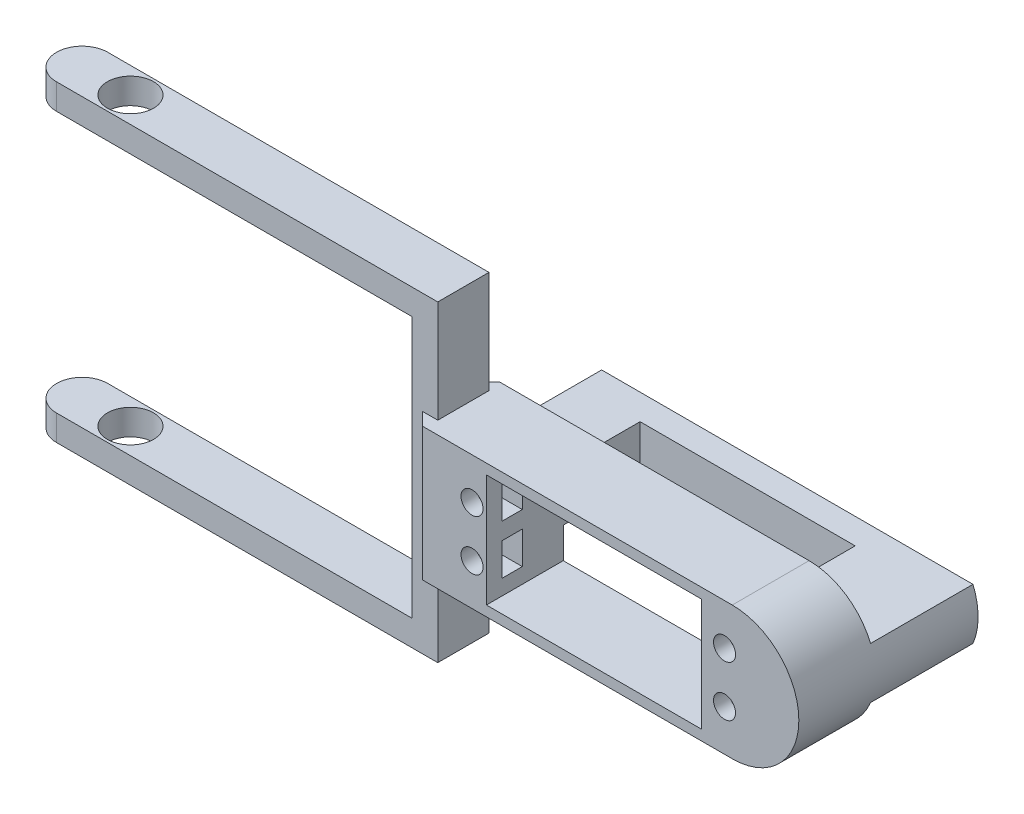
SolidWorks part; units mm, degrees
ref_plane "Plan de face" through (0, 0, 0) normal (0, 0, 1) x (1, 0, 0)
ref_plane "Plan de dessus" through (0, 0, 0) normal (0, 1, 0) x (1, 0, 0)
ref_plane "Plan de droite" through (0, 0, 0) normal (1, 0, 0) x (0, 0, -1)
sketch "Esquisse1" plane through (0, 0, 0) normal (0, 0, 1) x (1, 0, 0)
  line L1 (30, -13) -> (-30, -13)
  line L3 (30, 13) -> (-30, 13)
  line L4 (-30, -13) -> (-30, 13)
  line L5 (30, -13) -> (-30, 13) construction
  line L6 (30, 13) -> (-30, -13) construction
  arc A0 (30, -13) -> (30, 13) centre (30, 0) ccw
  point P0 (0, 0)
  dimension "D1" = 60
  dimension "D2" = 26
extrude "Boss.-Extru.1" add sketch "Esquisse1" along normal blind 15
sketch "Esquisse2" plane through (0, 0, 15) normal (0, 0, 1) x (1, 0, 0)
  line L0 (-30, 13) -> (-30, -13) construction
  line L1 (-18, 11) -> (24, 11)
  line L2 (-18, 11) -> (-18, -11)
  line L3 (-18, -11) -> (24, -11)
  line L4 (24, 11) -> (24, -11)
  point P4 (-18, 0)
  dimension "D1" = 42
  dimension "D2" = 22
  dimension "D3" = 12
extrude "Enlèv. mat.-Extru.1" cut sketch "Esquisse2" against normal through all
sketch "Esquisse4" plane through (0, 0, 15) normal (0, 0, 1) x (1, 0, 0)
  circle A0 centre (-20.81, 4.935) radius 2.15
  circle A1 centre (-20.81, -4.935) radius 2.15
  circle A2 centre (28.49, 4.935) radius 2.15
  circle A3 centre (28.49, -4.935) radius 2.15
extrude "Enlèv. mat.-Extru.2" cut sketch "Esquisse4" against normal blind 3
sketch "Esquisse5" plane through (-18, 0, 0) normal (1, 0, 0) x (0, 0, -1)
  line L1 (-12, -8) -> (-8, -8)
  line L2 (-12, -8) -> (-12, -1.65)
  line L3 (-12, -1.65) -> (-8, -1.65)
  line L4 (-8, -8) -> (-8, -1.65)
  line L5 (-15, 11) -> (-15, -11) construction
  line L6 (0, -11) -> (-15, -11) construction
  line L7 (-16.3207, 0) -> (1.751, 0) construction
  line L8 (-12, 1.65) -> (-8, 1.65)
  line L9 (-8, 8) -> (-8, 1.65)
  line L10 (-12, 8) -> (-8, 8)
  line L11 (-12, 8) -> (-12, 1.65)
  dimension "D1" = 6.35
  dimension "D2" = 4
  dimension "D3" = 3
  dimension "D4" = 3
extrude "Enlèv. mat.-Extru.3" cut sketch "Esquisse5" against normal blind 6
sketch "Esquisse6" plane through (24, 0, 0) normal (-1, 0, 0) x (0, 0, 1)
  line L0 (15, -11) -> (15, 11) construction
  line L1 (12, 8) -> (8, 8)
  line L2 (12, 8) -> (12, 1.65)
  line L3 (12, 1.65) -> (8, 1.65)
  line L4 (8, 8) -> (8, 1.65)
  line L5 (0, 11) -> (15, 11) construction
  line L6 (16.3207, 0) -> (-2.2889, 0) construction
  line L7 (12, -1.65) -> (8, -1.65)
  line L8 (8, -8) -> (8, -1.65)
  line L9 (12, -8) -> (8, -8)
  line L10 (12, -8) -> (12, -1.65)
  dimension "D1" = 6.35
  dimension "D2" = 4
  dimension "D3" = 3
  dimension "D4" = 3
extrude "Enlèv. mat.-Extru.4" cut sketch "Esquisse6" against normal blind 8
ref_plane "Plan1" through (0, 0, 7.5) normal (0, 0, 1) x (1, 0, 0)
sketch "Esquisse9" plane through (0, 0, 7.5) normal (0, 0, 1) x (1, 0, 0)
  line L1 (-30, 33) -> (-95, 33)
  line L2 (-95, 33) -> (-95, 28)
  line L3 (-95, 28) -> (-35, 28)
  line L5 (-35, 0) -> (-35, 28)
  line L6 (-95, -23) -> (-35, -23)
  line L7 (-30, -28) -> (-95, -28)
  line L8 (-95, -28) -> (-95, -23)
  line L9 (-30, 0) -> (-30, 33)
  line L10 (-30, 13) -> (-30, -13) construction
  line L11 (-30, -28) -> (-30, 0)
  line L12 (-35, 0) -> (-35, -23)
  point P9 (-30, 0)
  point P10 (-35, 0)
  point P12 (-30, 0)
  dimension "D1" = 28
  dimension "D2" = 5
  dimension "D3" = 33
  dimension "D4" = 23
  dimension "D5" = 5
  dimension "D6" = 65
  dimension "D7" = 60
extrude "Boss.-Extru.2" add sketch "Esquisse9" along normal blind 5 and the other way blind 5
chamfer "Chanfrein1" distance 3 angle 45 2 edges at (-30, 0, 12.5) (-30, 0, 2.5)
sketch "Esquisse11" plane through (0, -28, 0) normal (0, -1, 0) x (1, 0, 0)
  line L0 (-95, 2.5) -> (-95, 12.5)
  line L1 (-95, 2.5) -> (-104.4348, 2.5)
  line L2 (-95, 12.5) -> (-104.4348, 12.5)
  arc A1 (-104.4348, 2.5) -> (-104.4348, 12.5) centre (-104.4348, 7.5) cw
extrude "Boss.-Extru.4" add sketch "Esquisse11" against normal blind 5
sketch "Esquisse13" plane through (0, 0, 0) normal (0, 0, -1) x (-1, 0, 0)
  line L0 (18, 0) -> (30.5, 0) construction
  line L1 (18, 11) -> (18, -11) construction
  line L2 (30.5, -13) -> (30.5, 13) construction
  line L3 (-24, -11) -> (-24, 11) construction
  line L4 (30.5, -5) -> (18, -5)
  line L5 (30.5, -5) -> (30.5, 5)
  line L6 (30.5, 5) -> (18, 5)
  line L7 (18, -5) -> (18, 5)
  line L8 (30.5, -5) -> (18, 5) construction
  line L9 (30.5, 5) -> (18, -5) construction
  line L17 (18, 5) -> (-24, 5) construction
  line L18 (18, -5) -> (-24, -5) construction
  line L20 (-23.5605, 5) -> (-42, 5)
  line L21 (-24, -5) -> (-42, -5)
  line L22 (-24, 5) -> (-24, -5)
  arc A3 (-30, 13) -> (-30, -13) centre (-30, 0) ccw construction
  arc A4 (-42, 5) -> (-42, -5) centre (-30, 0) ccw
  point P6 (24.25, 0)
  line M10 (18, 11) -> (18, -11)
  line M12 (-24, -11) -> (-24, 11)
  line M14 (30.5, -13) -> (30.5, 13)
  arc M16 (-30, 13) -> (-30, -13) centre (-30, 0) ccw
  dimension "D1" = 10
extrude "Boss.-Extru.6" add sketch "Esquisse13" along normal blind 20 contours L21 L20 M12 M16 | L6 L4 M14 M10 region at (-24.25, 0, 0) region at (33.3383, 0, 0)
sketch "Esquisse14" plane through (0, 0, -20) normal (0, 0, -1) x (-1, 0, 0)
  line L1 (-24, 5) -> (18, 5)
  line L2 (-24, 5) -> (-24, -5)
  line L3 (-24, -5) -> (18, -5)
  line L4 (18, 5) -> (18, -5)
extrude "Boss.-Extru.7" add sketch "Esquisse14" against normal blind 5
sketch "Esquisse16" plane through (0, 33, 0) normal (0, 1, 0) x (1, 0, 0)
  line L0 (-35, -12.5) -> (-104.4348, -12.5) construction
  line L1 (-35, -2.5) -> (-104.4348, -2.5) construction
  line L2 (-89.416, -12.5) -> (-104.4348, -12.5)
  line L3 (-89.416, -2.5) -> (-104.4348, -2.5)
  line L4 (-89.416, -2.5) -> (-89.416, -12.5)
  arc A0 (-104.4348, -2.5) -> (-104.4348, -12.5) centre (-104.4348, -7.5) ccw construction
  arc A1 (-104.4348, -2.5) -> (-104.4348, -12.5) centre (-104.4348, -7.5) ccw
extrude "Boss.-Extru.8" add sketch "Esquisse16" against normal blind 5
sketch "Esquisse17" plane through (0, -28, 0) normal (0, -1, 0) x (1, 0, 0)
  circle A2 centre (-95, 7.5) radius 4.5
  arc A3 (-104.4348, 12.5) -> (-104.4348, 2.5) centre (-104.4348, 7.5) ccw construction
  dimension "D1" = 9
  dimension "D2" = 9.4348
extrude "Enlèv. mat.-Extru.5" cut sketch "Esquisse17" against normal through all
